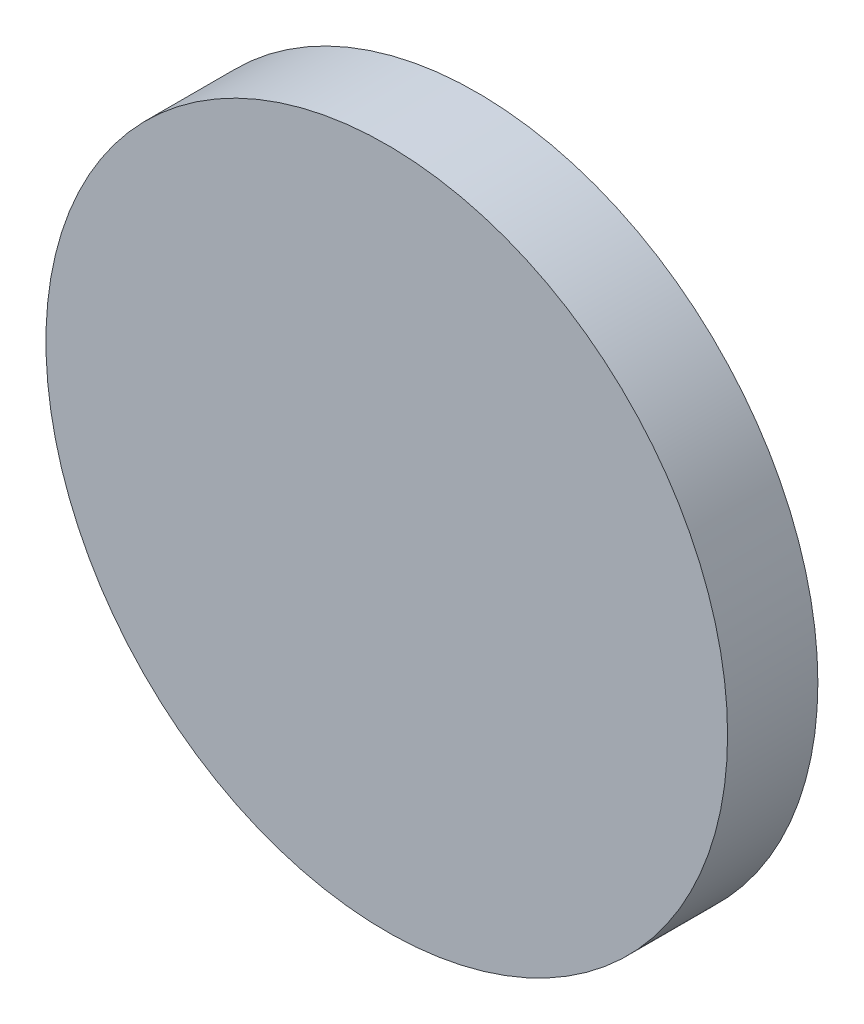
SolidWorks part; units mm, degrees
ref_plane "Front Plane" through (0, 0, 0) normal (0, 0, 1) x (1, 0, 0)
ref_plane "Top Plane" through (0, 0, 0) normal (0, 1, 0) x (1, 0, 0)
ref_plane "Right Plane" through (0, 0, 0) normal (1, 0, 0) x (0, 0, -1)
sketch "Sketch1" plane through (0, 0, 0) normal (0, 0, 1) x (1, 0, 0)
  circle A0 centre (0, 0) radius 2.55
  circle A1 centre (0, 0) radius 2.35
  circle A3 centre (0, 0) radius 2.35 construction
  circle A4 centre (0, 0) radius 4.55
  dimension "D1" = 0
  dimension "D2" = 0.2
  dimension "D3" = 2
extrude "Boss-Extrude1" add sketch "Sketch1" against normal blind 1.75
sketch "Sketch2" plane through (0, 0, 0) normal (0, 0, 1) x (1, 0, 0)
  circle A2 centre (0, 0) radius 7.55
  circle A3 centre (0, 0) radius 7.55
  dimension "D1" = 3
extrude "Boss-Extrude2" add sketch "Sketch2" along normal blind 2
